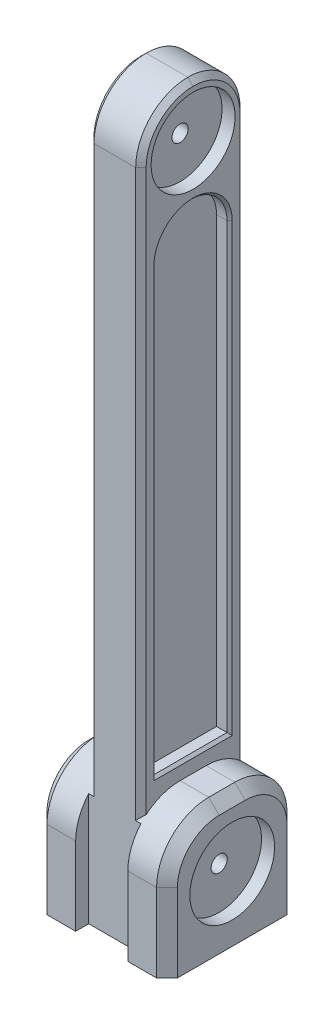
SolidWorks part; units mm, degrees
ref_plane "Front Plane" through (0, 0, 0) normal (0, 0, 1) x (1, 0, 0)
ref_plane "Top Plane" through (0, 0, 0) normal (0, 1, 0) x (1, 0, 0)
ref_plane "Right Plane" through (0, 0, 0) normal (1, 0, 0) x (0, 0, -1)
sketch "Base" plane through (0, 0, 0) normal (0, 1, 0) x (1, 0, 0)
  line L0 (0, 0) -> (0, 9.385) construction
  line L1 (0, 0) -> (8.4405, 0) construction
  line L2 (-5, 10) -> (5, 10)
  line L3 (-5, -10) -> (5, -10)
  line L4 (-5, 10) -> (-5, -10)
  line L5 (5, 10) -> (5, -10)
  line L6 (5, 10) -> (5, 12.5)
  line L7 (5, 12.5) -> (12.5, 12.5)
  line L8 (12.5, 12.5) -> (12.5, -12.5)
  line L9 (12.5, -12.5) -> (5, -12.5)
  line L10 (5, -12.5) -> (5, -10)
  line L11 (-5, -12.5) -> (-5, -10)
  line L12 (-12.5, -12.5) -> (-5, -12.5)
  line L13 (-12.5, 12.5) -> (-12.5, -12.5)
  line L14 (-5, 12.5) -> (-12.5, 12.5)
  line L15 (-5, 10) -> (-5, 12.5)
  point P20 (12.5, 0)
  dimension "D1" = 25
  dimension "D2" = 20
  dimension "D3" = 25
  dimension "D4" = 10
extrude "Boss-Extrude1" add sketch "Base" along normal blind 25 contours L10 L9 L8 L7 L6 L5 | L5 L2 L4 L3 | L4 L15 L14 L13 L12 L11 region at (0, 0, 0) region at (-8.75, 0, 0) region at (8.75, 0, 0)
sketch "Sketch2" plane through (-12.5, 0, 0) normal (-1, 0, 0) x (0, 0, 1)
  line L0 (0, 2.5) -> (0, 26.3184) construction
  line L2 (-12.5, 12.5) -> (12.5, 12.5) construction
  line L3 (-12.5, 25) -> (-12.5, 0) construction
  line L4 (12.5, 25) -> (12.5, 0) construction
  circle A0 centre (0, 12.5) radius 8.125
  circle A1 centre (0, 12.5) radius 1.55
  point P8 (0, 12.5)
  dimension "D1" = 16.25
  dimension "D2" = 3.1
extrude "Cut-Extrude1" cut sketch "Sketch2" against normal blind 2.5
extrude "Cut-Extrude2" cut sketch "Sketch2<2>" against normal through all contours A1 region at (-12.5, 12.5, 0)
sketch "Sketch2<2>" plane through (-12.5, 0, 0) normal (-1, 0, 0) x (0, 0, 1) same geometry as "Sketch2"
extrude "Boss-Extrude2" add sketch "Base<3>" along normal blind 115 from surface contours L5 L2 L4 L3 region at (0, 0, 0) starting at face at (0, 25, 0)
sketch "Base<3>" plane through (0, 0, 0) normal (0, 1, 0) x (1, 0, 0) same geometry as "Base"
ref_plane "Mid_Plane" through (0, 0, 0) normal (-1, 0, 0) x (0, 0, 1)
sketch "Bearing" plane through (-5, 0, 0) normal (-1, 0, 0) x (0, 0, 1)
  line L0 (0, 140) -> (0, 25) construction
  line L1 (10, 140) -> (-10, 140) construction
  line L2 (10, 25) -> (-10, 25) construction
  line L3 (-10, 138) -> (10, 138) construction
  line L4 (-10, 140) -> (-10, 25) construction
  line L5 (10, 140) -> (10, 25) construction
  circle A0 centre (0, 129.95) radius 8.05
  circle A1 centre (0, 129.95) radius 1.55
  dimension "D1" = 16.1
  dimension "D2" = 2
  dimension "D3" = 3.1
mirror "Mirror1" about plane through (0, 0, 0) normal (-1, 0, 0) of "Cut-Extrude1"
extrude "Cut-Extrude3" cut sketch "Bearing" against normal blind 2.5
fillet "Fillet1" radius 10 6 edges at (8.75, 25, -12.5) (-8.75, 25, -12.5) (-8.75, 25, 12.5) (8.75, 25, 12.5) (0, 140, -10) (0, 140, 10)
chamfer "Chamfer1" distance 2 angle 45 10 edges at (12.5, 7.5, 12.5) (12.5, 22.0711, 9.5711) (12.5, 25, 0) (12.5, 22.0711, -9.5711) (12.5, 7.5, -12.5) (-12.5, 7.5, 12.5) (-12.5, 22.0711, 9.5711) (-12.5, 25, 0) (-12.5, 22.0711, -9.5711) (-12.5, 7.5, -12.5)
sketch "Sketch4" plane through (5, 0, 0) normal (1, 0, 0) x (0, 0, -1)
  line L0 (0, 0) -> (0, 83.3525) construction
  line L1 (-7, 28) -> (7, 28)
  line L2 (7, 112.95) -> (7, 28)
  line L3 (-7, 112.95) -> (-7, 28)
  line L4 (10, 130) -> (10, 21.6144) construction
  line L5 (-2.5, 25) -> (2.5, 25) construction
  line L6 (7, 112.95) -> (-7, 112.95) construction
  arc A2 (7, 112.95) -> (-7, 112.95) centre (0, 112.95) ccw
  circle A3 centre (0, 129.95) radius 8.05 construction
  point P1 (0, 0)
  dimension "D3" = 17
  dimension "D1" = 3
  dimension "D2" = 3
extrude "Cut-Extrude5" cut sketch "Sketch4" against normal blind 2.5
mirror "Mirror2" about plane through (0, 0, 0) normal (-1, 0, 0) of "Cut-Extrude3", "Cut-Extrude5"
extrude "Cut-Extrude6" cut sketch "Bearing<2>" against normal through all contours A1
sketch "Bearing<2>" plane through (-5, 0, 0) normal (-1, 0, 0) x (0, 0, 1) same geometry as "Bearing"
chamfer "Chamfer2" distance 1 angle 45 8 edges at (5, 75.8072, -10) (5, 137.0711, -7.0711) (5, 137.0711, 7.0711) (5, 75.8072, 10) (-5, 75.8072, -10) (-5, 137.0711, -7.0711) (-5, 137.0711, 7.0711) (-5, 75.8072, 10)
chamfer "Chamfer3" distance 0.5 angle 45 8 edges at (-5, 70.475, -7) (-5, 119.95, 0) (-5, 70.475, 7) (-5, 28, 0) (5, 70.475, 7) (5, 119.95, 0) (5, 28, 0) (5, 70.475, -7)
